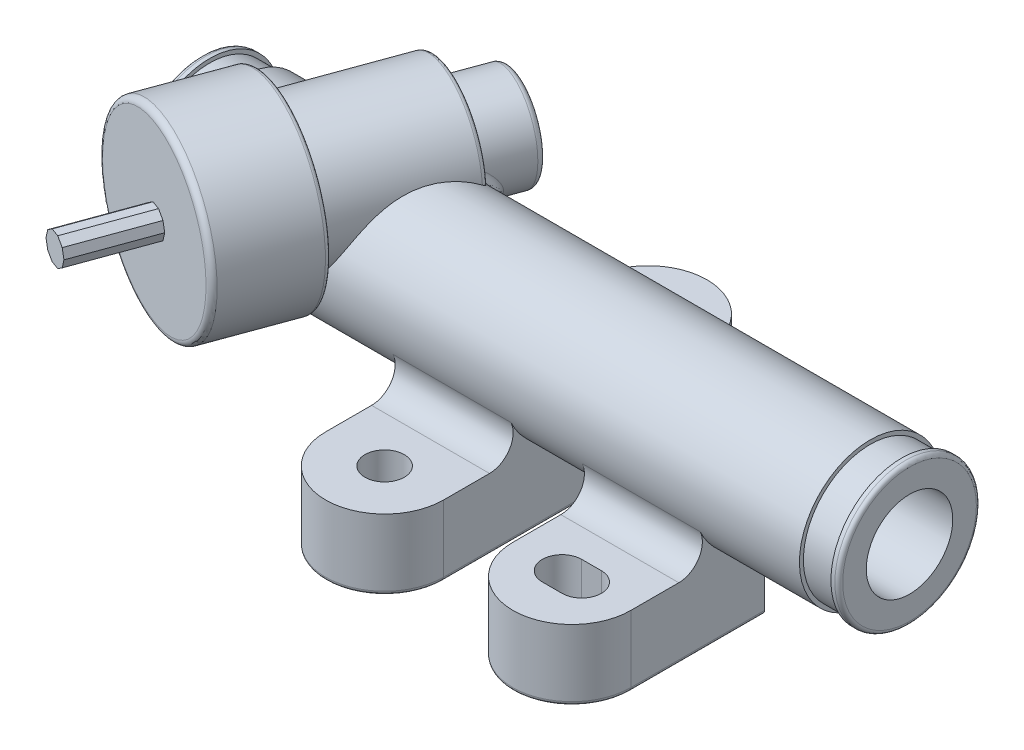
SolidWorks part; units mm, degrees
material "Alloy Steel"
ref_plane "Front Plane" through (0, 0, 0) normal (0, 0, 1) x (1, 0, 0)
ref_plane "Top Plane" through (0, 0, 0) normal (0, 1, 0) x (1, 0, 0)
ref_plane "Right Plane" through (0, 0, 0) normal (1, 0, 0) x (0, 0, -1)
sketch "Sketch1" plane through (0, 0, 0) normal (1, 0, 0) x (0, 0, -1)
  circle A0 centre (0, 0) radius 11
  circle A1 centre (0, 0) radius 18
  dimension "D1" = 22
  dimension "D2" = 36
extrude "Boss-Extrude1" add sketch "Sketch1" along normal blind 180
ref_plane "Plane1" through (0, -18, 0) normal (0, 1, 0) x (1, 0, 0)
sketch "Sketch2" plane through (0, -18, 0) normal (0, 1, 0) x (1, 0, 0)
  line L0 (80, 33.5) -> (80, -33.5)
  line L1 (0, 18) -> (0, -18) construction
  line L2 (0, 0) -> (124.4097, 0)
  line L3 (113.1301, -34.0071) -> (113.1301, 0)
  line L6 (80, 33.5) -> (80, -33.5) construction
  line L7 (95, 33.5) -> (95, -33.5)
  line L8 (65, 33.5) -> (65, -33.5)
  line L14 (125.6301, -34.0071) -> (130.6301, -34.0071) construction
  line L15 (125.6301, -39.0071) -> (130.6301, -39.0071)
  line L16 (125.6301, -29.0071) -> (130.6301, -29.0071)
  line L17 (113.1301, 0) -> (143.1301, 0)
  line L18 (143.1301, 0) -> (143.1301, -34.0071)
  circle A0 centre (80, 33.5) radius 5
  circle A1 centre (80, -33.5) radius 5
  arc A5 (95, 33.5) -> (65, 33.5) centre (80, 33.5) ccw
  arc A6 (65, -33.5) -> (95, -33.5) centre (80, -33.5) ccw
  arc A9 (125.6301, -39.0071) -> (125.6301, -29.0071) centre (125.6301, -34.0071) cw
  arc A10 (130.6301, -29.0071) -> (130.6301, -39.0071) centre (130.6301, -34.0071) cw
  arc A14 (113.1301, -34.0071) -> (143.1301, -34.0071) centre (128.1301, -34.0071) ccw
  point P9 (80, 0)
  point P33 (128.1301, -34.0071)
  dimension "D1" = 67
  dimension "D2" = 10
  dimension "D3" = 10
  dimension "D6" = 30
  dimension "D7" = 15
  dimension "D4" = 80
  dimension "D5" = 33.5
extrude "Boss-Extrude2" add sketch "Sketch2" against normal blind 16 and the other way blind 2 contours A10 L16 A9 L15 | A14 L18 L17 L3 | L8 A6 L7 A5 | A0 | A1 region at (128.1301, -18, 34.0071)
sketch "Sketch3" plane through (180, 0, 0) normal (1, 0, 0) x (0, 0, -1)
  circle A0 centre (0, 0) radius 11
extrude "Cut-Extrude1" [suppressed] cut sketch "Sketch3" against normal through all
ref_plane "Plane2" through (50, 0, 0) normal (-1, 0, 0) x (0, 0, 1)
sketch "Sketch4" plane through (50, 0, 0) normal (-1, 0, 0) x (0, 0, 1)
  line L0 (0, 0) -> (0, 8.423)
ref_plane "Plane3" through (5.8489, 0, -16.0697) normal (-0.342, 0, 0.9397) x (0, 1, 0)
sketch "Sketch5" plane through (5.8489, 0, -16.0697) normal (-0.342, 0, 0.9397) x (0, 1, 0)
  circle A0 centre (13.0934, -37.4923) radius 17.5
  dimension "D1" = 35
extrude "Boss-Extrude3" add sketch "Sketch5" along normal blind 20 and the other way blind 14
sketch "Sketch6" plane through (-0.9915, 0, 2.7242) normal (-0.342, 0, 0.9397) x (0.9397, 0, 0.342)
  circle A0 centre (37.4923, 13.0934) radius 23.5
  dimension "D1" = 47
extrude "Boss-Extrude4" add sketch "Sketch6" along normal blind 24
sketch "Sketch7" plane through (10.6372, 0, -29.2254) normal (0.342, 0, -0.9397) x (-0.9397, 0, -0.342)
  circle A0 centre (-37.4923, 13.0934) radius 12
  dimension "D1" = 24
extrude "Boss-Extrude5" add sketch "Sketch7" along normal blind 14
fillet "Fillet2" [suppressed] radius 10
sketch "Sketch8" plane through (-9.2, 0, 25.2768) normal (-0.342, 0, 0.9397) x (0.9397, 0, 0.342)
  line L1 (41.9107, 13.5097) -> (41.1827, 15.7501)
  line L2 (41.1827, 15.7501) -> (39.277, 17.1347)
  line L3 (39.277, 17.1347) -> (36.9213, 17.1347)
  line L4 (36.9213, 17.1347) -> (35.0155, 15.7501)
  line L5 (35.0155, 15.7501) -> (34.2876, 13.5097)
  line L6 (34.2876, 13.5097) -> (35.0155, 11.2694)
  line L7 (35.0155, 11.2694) -> (36.9213, 9.8847)
  line L8 (36.9213, 9.8847) -> (39.277, 9.8847)
  line L9 (39.277, 9.8847) -> (41.1827, 11.2694)
  line L10 (41.1827, 11.2694) -> (41.9107, 13.5097)
  circle A0 centre (38.0991, 13.5097) radius 3.625 construction
extrude "Boss-Extrude6" add sketch "Sketch8" along normal blind 20
sketch "Sketch9" plane through (0, 0, 0) normal (0, 1, 0) x (1, 0, 0)
  line L0 (0, -18) -> (12.5802, -18) construction
  line L1 (2, -18) -> (10, -18)
  line L2 (2, -18) -> (2, -17)
  line L3 (2, -17) -> (10, -17)
  line L4 (10, -18) -> (10, -17)
  line L5 (180, -18) -> (180, 18) construction
  line L6 (178, -18) -> (170, -18)
  line L7 (178, -18) -> (178, -17)
  line L8 (178, -17) -> (170, -17)
  line L9 (170, -18) -> (170, -17)
  line L10 (0, 18) -> (0, -18) construction
  dimension "D1" = 1
  dimension "D2" = 8
  dimension "D3" = 1
  dimension "D4" = 8
  dimension "D5" = 2
  dimension "D6" = 2
revolve "Cut-Revolve1" cut sketch "Sketch9" angle 360 about axis through (180, 0, 0) along (-1, 0, 0)
fillet "Fillet3" radius 1.5 5 edges at (54.3231, 3.7529, -17.6044) (39.4915, 22.9903, -18.7233) (39.3803, 13.0934, -33.6622) (48.114, 13.0934, 46.1374) (44.3436, 26.9005, 19.2248)
fillet "Fillet4" radius 1 11 edges at (95, -34, 0) (65, -34, 0) (113.1301, -34, 17.0036) (143.1301, -34, 17.0036) (34.8327, 26.0675, -20.4189) (51.5798, 27.6446, 21.8585) (0, 0, -18) (80, -34, -48.5) (180, 0, -18) (128.1301, -34, 49.0071) (80, -34, 48.5)
fillet "Fillet5" radius 6 3 edges at (128.1301, -16, 8.2462) (80, -16, -8.2462) (80, -16, 8.2462)
sketch "Sketch10" plane through (0, 0, 0) normal (-1, 0, 0) x (0, 0, 1)
  circle A0 centre (0, 0) radius 11
  circle A2 centre (0, 0) radius 11 construction
extrude "Cut-Extrude2" cut sketch "Sketch10" against normal blind 100
sketch3d "3DSketch1"
  line L0 (180, 0, 0) -> (0, 0, 0) construction
  point P0 (90, 0, 0)
  point P1 (0, 0, 0)
